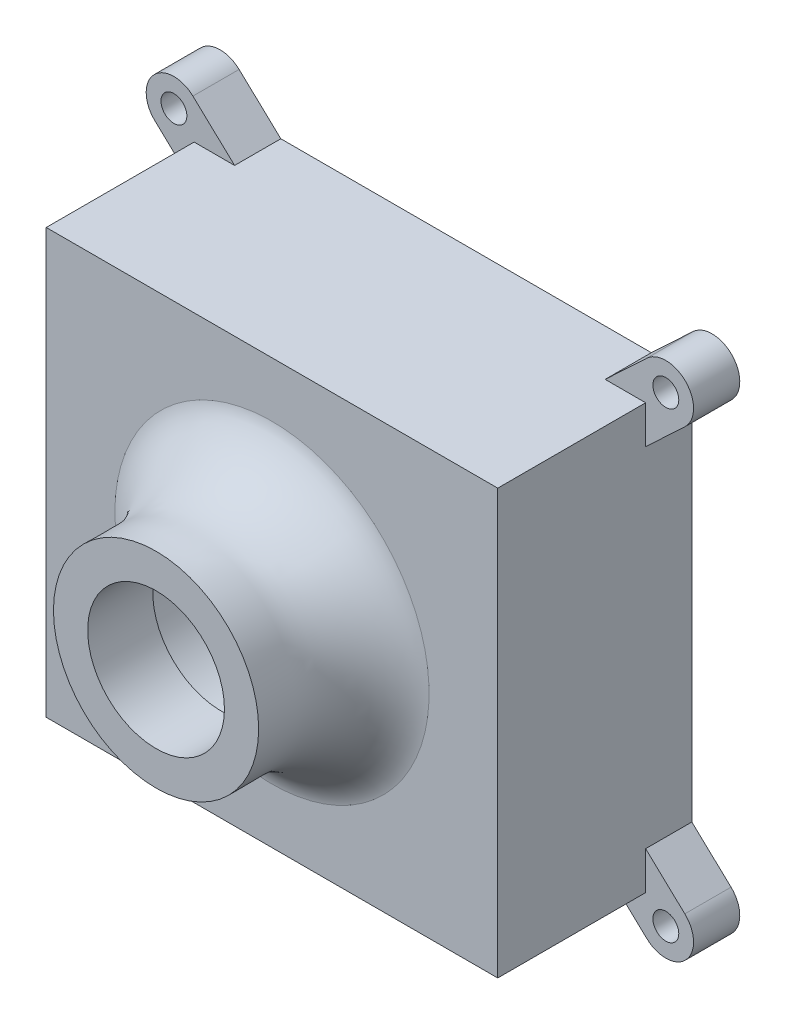
SolidWorks part; units mm, degrees
ref_plane "前视基准面" through (0, 0, 0) normal (0, 0, 1) x (1, 0, 0)
ref_plane "上视基准面" through (0, 0, 0) normal (0, 1, 0) x (1, 0, 0)
ref_plane "右视基准面" through (0, 0, 0) normal (1, 0, 0) x (0, 0, -1)
sketch "草图1" plane through (0, 0, 0) normal (0, 0, 1) x (1, 0, 0)
  line L0 (0, 20.95) -> (0, -20.95) construction
  line L1 (-22.425, 20.95) -> (22.425, 20.95)
  line L2 (-22.425, 20.95) -> (-22.425, -20.95)
  line L3 (-22.425, -20.95) -> (22.425, -20.95)
  line L4 (22.425, 20.95) -> (22.425, -20.95)
  line L5 (-22.425, 0) -> (22.425, 0) construction
  line L6 (-24.425, 22.95) -> (24.425, 22.95)
  line L7 (-15.275, -15.275) -> (15.275, -15.275)
  line L8 (-15.275, -15.275) -> (-15.275, 15.275)
  line L9 (-15.275, 15.275) -> (15.275, 15.275)
  line L10 (15.275, -15.275) -> (15.275, 15.275)
  line L11 (-15.275, -15.275) -> (15.275, 15.275) construction
  line L12 (-15.275, 15.275) -> (15.275, -15.275) construction
  line L13 (24.425, 22.95) -> (24.425, -22.95)
  line L14 (-24.425, -22.95) -> (24.425, -22.95)
  line L15 (-24.425, 22.95) -> (-24.425, -22.95)
  line L16 (-24.425, 22.95) -> (24.425, -22.95) construction
  line L17 (7.0496, -2.25) -> (11.5496, -2.25)
  line L18 (7.0496, -2.25) -> (7.0496, 2.25) construction
  line L19 (7.0496, 2.25) -> (11.5496, 2.25)
  line L20 (11.5496, -2.25) -> (11.5496, 2.25)
  line L21 (7.0496, -2.25) -> (11.5496, 2.25) construction
  line L22 (7.0496, 2.25) -> (11.5496, -2.25) construction
  line L23 (24.425, 22.95) -> (-24.425, -22.95) construction
  line L24 (-28.6656, 22.818) -> (-24.425, 18.8335)
  line L25 (-24.557, 27.1906) -> (-20.0439, 22.95)
  line L26 (-24.557, -27.1906) -> (-20.0439, -22.95)
  line L27 (-28.6656, -22.818) -> (-24.425, -18.8335)
  line L28 (28.6656, -22.818) -> (24.425, -18.8335)
  line L29 (24.557, -27.1906) -> (20.0439, -22.95)
  line L30 (24.557, 27.1906) -> (20.0439, 22.95)
  line L31 (28.6656, 22.818) -> (24.425, 18.8335)
  circle A0 centre (0, 0) radius 7.4
  circle A1 centre (0, 0) radius 11.25
  circle A2 centre (0, 0) radius 9.05
  circle A3 centre (-26.6113, 25.0043) radius 1.4
  circle A4 centre (-26.6113, 25.0043) radius 3
  circle A5 centre (-26.6113, -25.0043) radius 3
  circle A6 centre (-26.6113, -25.0043) radius 1.4
  circle A7 centre (26.6113, -25.0043) radius 1.4
  circle A8 centre (26.6113, -25.0043) radius 3
  circle A9 centre (26.6113, 25.0043) radius 3
  circle A10 centre (26.6113, 25.0043) radius 1.4
  point P8 (0, 0)
  point P22 (9.2996, 0)
  dimension "D4" = 14.8
  dimension "D6" = 22.5
  dimension "D7" = 18.1
  dimension "D10" = 2.8
  dimension "D1" = 44.85
  dimension "D2" = 41.9
  dimension "D3" = 30.55
  dimension "D8" = 4.5
  dimension "D9" = 4.5
  dimension "D11" = 3
  dimension "D5" = 2
extrude "凸台-拉伸1" add sketch "草图1" against normal blind 18 contours L6 L15 L14 L13 L1 L4 L3 L2 region at (-22.2344, 22.2797, 0)
extrude "凸台-拉伸2" add sketch "草图1<4>" along normal blind 3 contours L6 L15 L14 L13 L1 L4 L3 L2 | L4 L1 L2 L3 L10 L7 L8 L9 | L7 L10 L9 L8 A1 region at (0, 20.3362, 0) region at (-22.2344, 22.2797, 0) region at (-14.843, 0, 0)
sketch "草图1<4>" plane through (0, 0, 0) normal (0, 0, 1) x (1, 0, 0) same geometry as "草图1"
extrude "切除-拉伸1" cut sketch "草图1<6>" along normal blind 0.5 contours L7 L10 L9 L8 A1 region at (-14.843, 0, 0)
sketch "草图1<6>" plane through (0, 0, 0) normal (0, 0, 1) x (1, 0, 0) same geometry as "草图1"
sketch "草图2" plane through (0, 0, 0) normal (0, -1, 0) x (1, 0, 0)
  line L0 (0, 0) -> (0, 11.4599) construction
  line L1 (-11.1, 15.5434) -> (0, 15.5434)
  line L2 (0, 15.5434) -> (0, 3.0434)
  line L3 (0, 3.0434) -> (-17, 3)
  line L4 (-24.425, 3) -> (24.425, 3) construction
  spline S0 degree 3 poles (-11.1, 15.5434) (-11.0457, 13.7003) (-11.1112, 13.5973) (-11.0014, 8.512) (-14.1814, 3.5427) (-17, 3) knots 0 0 0 0 0.386915 0.486915 1 1 1 1
  dimension "D1" = 11.1
  dimension "D2" = 17
  dimension "D3" = 12.5
revolve "旋转2" add sketch "草图2" angle 360 about L0 region at (-6.1968, 0, 8.898)
extrude "切除-拉伸2" cut sketch "草图1<7>" against normal through all from surface contours A0 starting at face at (-11.1, 0, 15.5434)
sketch "草图1<7>" plane through (0, 0, 0) normal (0, 0, 1) x (1, 0, 0) same geometry as "草图1"
extrude "切除-拉伸6" cut sketch "草图1<9>" along normal blind 3 from surface contours A1 A2 L19 L20 L17 | A2 L17 L20 L19 | L17 A2 L19 A0 | L19 A2 L17 A0 region at (8.119, 0, 0) region at (7.9077, -2.504, 0) region at (10.0646, 0, 0) region at (9.8943, -2.5666, 0) starting at face at (5.718, 0, 0.5)
sketch "草图1<9>" plane through (0, 0, 0) normal (0, 0, 1) x (1, 0, 0) same geometry as "草图1"
extrude "切除-拉伸8" cut sketch "草图1<10>" along normal blind 5 from surface contours A2 L17 L20 L19 | L17 A2 L19 A0 | L19 A2 L17 A0 region at (8.119, 0, 0) region at (7.9077, -2.504, 0) region at (10.0646, 0, 0) starting at face at (11.25, 0, 3.5)
sketch "草图1<10>" plane through (0, 0, 0) normal (0, 0, 1) x (1, 0, 0) same geometry as "草图1"
extrude "凸台-拉伸3" add sketch "草图1<11>" along normal blind 5 from surface contours A9 A10 | L6 A9 L30 | L31 A9 L13 | A8 A7 | A8 L14 L29 | A8 L28 L13 | A5 A6 | L14 A5 L26 | L27 A5 L15 | A4 L24 L15 | A4 L6 L25 | A4 A3 region at (-22.5782, 24.0892, 0) region at (-25.5484, 21.1193, 0) region at (-26.5206, 22.0905, 0) region at (22.5782, 24.0892, 0) region at (-25.5484, -21.1193, 0) region at (25.5484, 21.1193, 0) region at (23.6976, 25.095, 0) region at (-22.5782, -24.0892, 0) region at (-23.901, -23.9307, 0) region at (25.5484, -21.1193, 0) region at (22.5782, -24.0892, 0) region at (26.5206, -22.0905, 0) starting at face at (0, 0, -18)
sketch "草图1<11>" plane through (0, 0, 0) normal (0, 0, 1) x (1, 0, 0) same geometry as "草图1"
fillet "圆角1" [suppressed] radius 3
fillet "圆角3" [suppressed] radius 3
fillet "圆角5" [suppressed] radius 3
fillet "圆角6" [suppressed] radius 1
